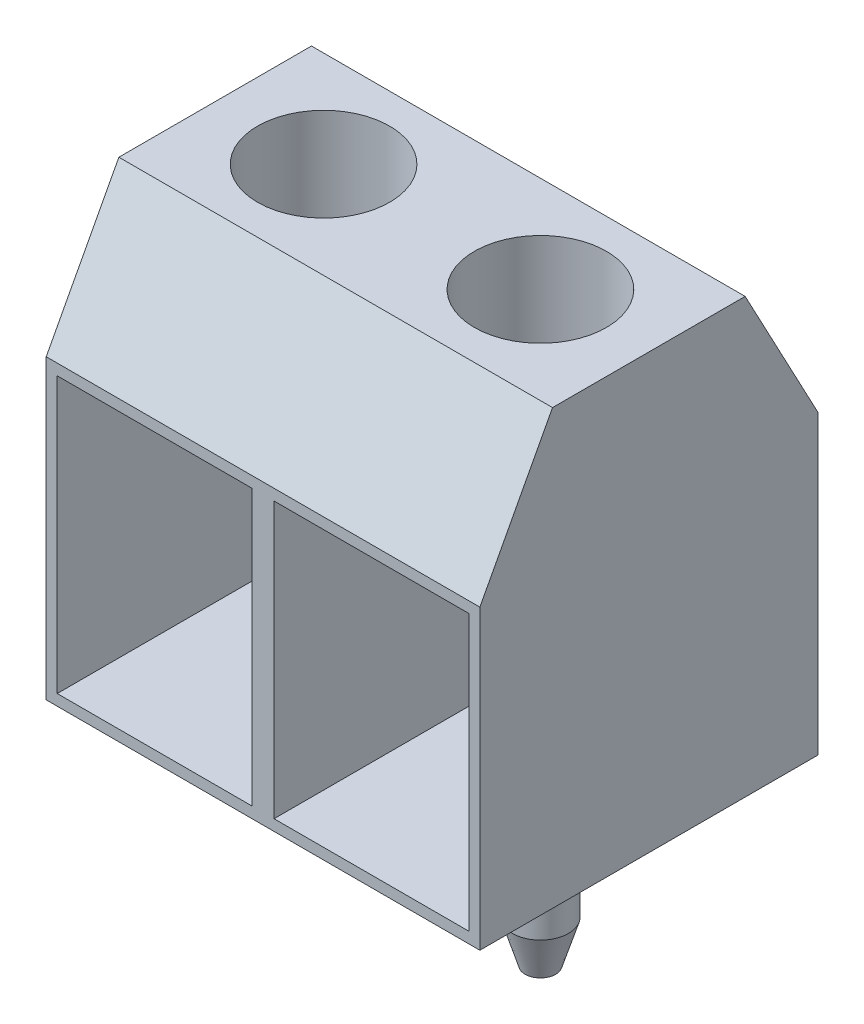
SolidWorks part; units mm, degrees
ref_plane "Front Plane" through (0, 0, 0) normal (0, 0, 1) x (1, 0, 0)
ref_plane "Top Plane" through (0, 0, 0) normal (0, 1, 0) x (1, 0, 0)
ref_plane "Right Plane" through (0, 0, 0) normal (1, 0, 0) x (0, 0, -1)
sketch "Sketch3" plane through (0, 0, 0) normal (0, 1, 0) x (1, 0, 0)
  line L1 (-5.0038, -3.8989) -> (5.0038, -3.8989)
  line L2 (-5.0038, -3.8989) -> (-5.0038, 3.8989)
  line L3 (-5.0038, 3.8989) -> (5.0038, 3.8989)
  line L4 (5.0038, -3.8989) -> (5.0038, 3.8989)
  line L5 (-5.0038, -3.8989) -> (5.0038, 3.8989) construction
  line L6 (-5.0038, 3.8989) -> (5.0038, -3.8989) construction
  point P0 (0, 0)
  dimension "D1" = 7.7978
  dimension "D2" = 10.0076
extrude "Boss-Extrude1" add sketch "Sketch3" along normal blind 10.0076
sketch "Sketch4" plane through (-5.0038, 0, 0) normal (-1, 0, 0) x (0, 0, 1)
  line L0 (-3.8989, 6.858) -> (-2.2225, 10.0076)
  line L1 (2.2225, 10.0076) -> (3.8989, 6.858)
  line L2 (-3.8989, 6.858) -> (3.8989, 6.858) construction
  line L4 (-3.8989, 0) -> (3.8989, 0)
  line L5 (3.8989, 0) -> (3.8989, 10.0076)
  line L6 (3.8989, 10.0076) -> (-3.8989, 10.0076)
  line L7 (-3.8989, 10.0076) -> (-3.8989, 0)
  line L8 (-3.8989, 0) -> (3.8989, 0)
  line L9 (3.8989, 0) -> (3.8989, 6.858)
  line L10 (2.2225, 10.0076) -> (-2.2225, 10.0076)
  line L11 (-3.8989, 6.858) -> (-3.8989, 0)
  line M9 (3.8989, 0) -> (3.8989, 10.0076)
  line M10 (3.8989, 10.0076) -> (-3.8989, 10.0076)
  line M11 (-3.8989, 10.0076) -> (-3.8989, 0)
  dimension "D2" = 6.858
  dimension "D3" = 4.445
  dimension "D1" = 0
extrude "Cut-Extrude1" cut sketch "Sketch4" against normal blind 10.0076 contours L0 M11 M10 | L1 M10 M9 region at (-5.0038, 8.9577, -3.3401) region at (-5.0038, 8.9577, 3.3401)
sketch "Sketch5" plane through (0, 10.0076, 0) normal (0, 1, 0) x (1, 0, 0)
  line L0 (0, 0) -> (2.5019, 0) construction
  line L1 (0, 0) -> (-2.5019, 0) construction
  circle A0 centre (-2.5019, 0) radius 1.524
  circle A1 centre (2.5019, 0) radius 1.524
  dimension "D2" = 3.048
  dimension "D1" = 5.0038
extrude "Cut-Extrude2" cut sketch "Sketch5" against normal blind 2.54
sketch "Sketch6" plane through (0, 0, 3.8989) normal (0, 0, 1) x (1, 0, 0)
  line L4 (0, 6.858) -> (0, 0) construction
  line L5 (-0.254, 6.604) -> (-0.254, 0.254)
  line L6 (0.254, 6.604) -> (0.254, 0.254)
  line L7 (-0.254, 6.604) -> (-4.7498, 6.604)
  line L8 (4.7498, 0.254) -> (4.7498, 6.604)
  line L9 (4.7498, 6.604) -> (-4.7498, 6.604)
  line L10 (-4.7498, 6.604) -> (-4.7498, 0.254)
  line L11 (-4.7498, 0.254) -> (4.7498, 0.254)
  line L12 (4.7498, 0.254) -> (4.7498, 6.604)
  line L13 (4.7498, 6.604) -> (0.254, 6.604)
  line L14 (-4.7498, 6.604) -> (-4.7498, 0.254)
  line L15 (-4.7498, 0.254) -> (-0.254, 0.254)
  line L16 (0.254, 0.254) -> (4.7498, 0.254)
  line L17 (0, 6.604) -> (0, 0.254) construction
  line L18 (-5.0038, 0) -> (5.0038, 0) construction
  line L19 (5.0038, 6.858) -> (-5.0038, 6.858) construction
  point P7 (0, 0)
  point P15 (0, 6.858)
  dimension "D1" = 0.254
  dimension "D2" = 0.254
  dimension "D3" = 0.254
extrude "Cut-Extrude3" cut sketch "Sketch6" against normal blind 5.08
sketch "Sketch8" plane through (0, 0, 0) normal (0, -1, 0) x (1, 0, 0)
  circle A0 centre (2.5019, 0) radius 1.524 construction
  circle A1 centre (-2.5019, 0) radius 1.524 construction
  circle A2 centre (2.5019, 0) radius 1.524 construction
  circle A3 centre (-2.5019, 0) radius 1.524 construction
  circle A4 centre (-2.5019, 0) radius 0.6477
  circle A5 centre (2.5019, 0) radius 0.6477
  dimension "D1" = 1.2954
extrude "Boss-Extrude2" add sketch "Sketch8" along normal blind 2.54
sketch "Sketch9" plane through (0, -2.54, 0) normal (0, -1, 0) x (1, 0, 0)
  circle A0 centre (-2.5019, 0) radius 0.6477 construction
  circle A1 centre (2.5019, 0) radius 0.6477
  circle A2 centre (2.5019, 0) radius 0.6477
  circle A3 centre (-2.5019, 0) radius 0.6477
  dimension "D1" = 0
extrude "Boss-Extrude3" add sketch "Sketch9" along normal blind 0.9652 draft 17
